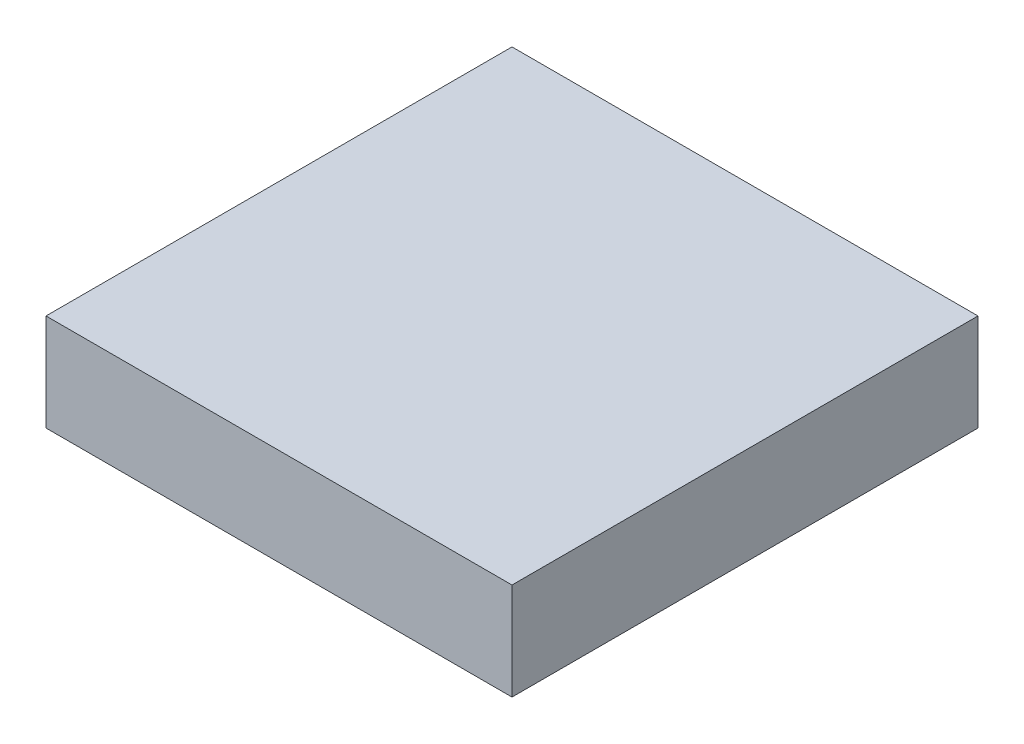
SolidWorks part; units mm, degrees
ref_plane "Front Plane" through (0, 0, 0) normal (0, 0, 1) x (1, 0, 0)
ref_plane "Top Plane" through (0, 0, 0) normal (0, 1, 0) x (1, 0, 0)
ref_plane "Right Plane" through (0, 0, 0) normal (1, 0, 0) x (0, 0, -1)
sketch "Sketch1" plane through (0, 0, 0) normal (0, 1, 0) x (1, 0, 0)
  line L1 (-60, -60) -> (60, -60)
  line L2 (-60, -60) -> (-60, 60)
  line L3 (-60, 60) -> (60, 60)
  line L4 (60, -60) -> (60, 60)
  line L5 (-60, -60) -> (60, 60) construction
  line L6 (-60, 60) -> (60, -60) construction
  point P0 (0, 0)
  dimension "D1" = 120
  dimension "D2" = 120
extrude "Boss-Extrude1" add sketch "Sketch1" along normal blind 25
